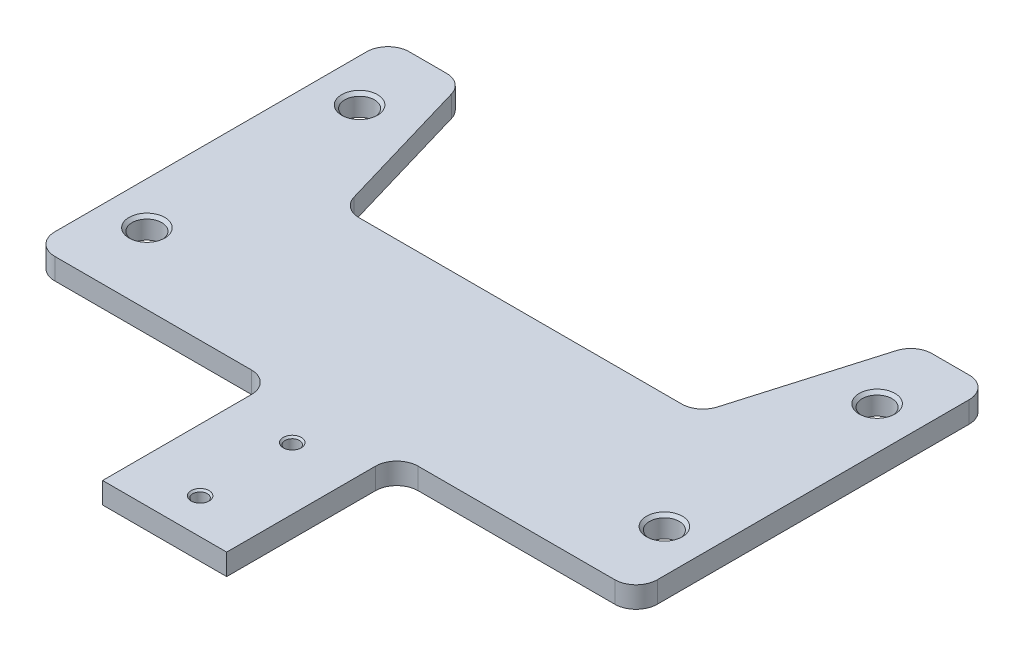
SolidWorks part; units mm, degrees
ref_plane "Front Plane" through (0, 0, 0) normal (0, 0, 1) x (1, 0, 0)
ref_plane "Top Plane" through (0, 0, 0) normal (0, 1, 0) x (1, 0, 0)
ref_plane "Right Plane" through (0, 0, 0) normal (1, 0, 0) x (0, 0, -1)
sketch "Sketch2" plane through (0, 0, 0) normal (0, 1, 0) x (1, 0, 0)
  line L1 (42.5, 0) -> (42.5, 50)
  line L2 (42.5, 50) -> (22.5, 50)
  line L3 (22.5, 50) -> (8.75, 26.1843)
  line L4 (8.75, 26.1843) -> (-8.75, 26.1843)
  line L5 (-8.75, 26.1843) -> (-22.5, 50)
  line L6 (-22.5, 50) -> (-42.5, 50)
  line L7 (-42.5, 50) -> (-42.5, 0)
  line L9 (-42.5, 0) -> (42.5, 0)
  point P0 (0, 26.1843)
  point P3 (0, 0)
  point P11 (32.5, 50)
  point P13 (-32.5, 50)
  dimension "D1" = 17.5
  dimension "D2" = 85
  dimension "D3" = 50
  dimension "D4" = 60
  dimension "D5" = 60
  dimension "D6" = 20
extrude "Boss-Extrude1" add sketch "Sketch2" along normal blind 3
sketch "Sketch3" plane through (0, 0, -26.1843) normal (0, 0, -1) x (-1, 0, 0)
  line L6 (-8.75, 0) -> (8.75, 0)
  line L7 (-8.75, 0) -> (-8.75, 1)
  line L8 (-8.75, 1) -> (8.75, 1)
  line L9 (8.75, 0) -> (8.75, 1)
  point P5 (0, 0)
  dimension "D1" = 17.5
  dimension "D2" = 1
extrude "Cut-Extrude1" [suppressed] cut sketch "Sketch3" against normal through all
sketch "Sketch10" plane through (0, 3, 0) normal (0, 1, 0) x (1, 0, 0)
  line L0 (-8.75, 0) -> (-8.75, -24)
  line L1 (-42.5, 0) -> (42.5, 0) construction
  line L2 (-8.75, -24) -> (8.75, -24)
  line L3 (8.75, -24) -> (8.75, 0)
  line L4 (8.75, 0) -> (-8.75, 0)
  point P4 (0, 0)
  dimension "D1" = 17.5
  dimension "D2" = 24
extrude "Boss-Extrude2" add sketch "Sketch10" against normal up to surface (3 mm away) up to face at (0, 0, -31.5461)
hole_wizard "M2.5x0.45 Tapped Hole1" positions "Sketch4" profile "Sketch5" tap size "M2.5x0.45" standard "ANSI Metric"
sketch "Sketch4" plane through (0, 3, 0) normal (0, 1, 0) x (1, 0, 0)
  line L4 (-8.75, -24) -> (8.75, -24) construction
  point P0 (0, -19)
  point P2 (0, -6)
  dimension "D1" = 13
  dimension "D2" = 5
  dimension "D3" = 8.75
sketch "Sketch5" plane through (0, 3, 19) normal (1, 0, 0) x (0, 0, 1)
  line L0 (0, 0) -> (0, 6.9659)
  line L1 (0, 6.9659) -> (1.025, 6.35)
  line L2 (1.025, 6.35) -> (1.025, 0.25)
  line L3 (1.025, 0.25) -> (1.275, 0)
  line L5 (1.275, 0) -> (0, 0)
  line L6 (-1.025, 0.25) -> (-1.275, 0) construction
  line L10 (0, 6.9659) -> (-1.025, 6.35) construction
  line L11 (0, -6.35) -> (0, 107.95) construction
  dimension "Tap Drill Dia." = 2.05
  dimension "Tap Drill Depth" = 6.35
  dimension "Near C'Sink Dia." = 2.55
  dimension "Near C'Sink Angle" = 90
  dimension "Drill Angle" = 118
cosmetic thread "Hole Thread1" parameters "D1"=5, "D2"=2.5
cosmetic thread "Hole Thread2" parameters "D1"=5, "D2"=2.5
hole_wizard "M5x0.8 Tapped Hole1" positions "Sketch6" profile "Sketch7" tap size "M5x0.8" standard "ANSI Metric"
sketch "Sketch6" plane through (0, 3, 0) normal (0, 1, 0) x (1, 0, 0)
  line L1 (-22.5, 50) -> (-42.5, 50) construction
  line L2 (42.5, 50) -> (22.5, 50) construction
  line L3 (42.5, 0) -> (42.5, 50) construction
  line L4 (-42.5, 50) -> (-42.5, 0) construction
  line L5 (-42.5, 0) -> (-8.75, 0) construction
  point P0 (-36.5, 40)
  point P2 (36.5, 40)
  point P18 (-36.5, 10)
  point P20 (36.5, 10)
  dimension "D1" = 6
  dimension "D2" = 10
  dimension "D3" = 10
  dimension "D4" = 6
  dimension "D5" = 10
  dimension "D6" = 10
sketch "Sketch7" plane through (-36.5, 3, -40) normal (1, 0, 0) x (0, 0, 1)
  line L0 (0, 0) -> (0, 13.6618)
  line L1 (0, 13.6618) -> (2.1, 12.4)
  line L2 (2.1, 12.4) -> (2.1, 0.425)
  line L3 (2.1, 0.425) -> (2.525, 0)
  line L5 (2.525, 0) -> (0, 0)
  line L6 (-2.1, 0.425) -> (-2.525, 0) construction
  line L10 (0, 13.6618) -> (-2.1, 12.4) construction
  line L11 (0, -6.35) -> (0, 107.95) construction
  dimension "Tap Drill Dia." = 4.2
  dimension "Tap Drill Depth" = 12.4
  dimension "Near C'Sink Dia." = 5.05
  dimension "Near C'Sink Angle" = 90
  dimension "Drill Angle" = 118
cosmetic thread "Hole Thread3" parameters "D1"=10, "D2"=5
cosmetic thread "Hole Thread4" parameters "D1"=10, "D2"=5
cosmetic thread "Hole Thread5" parameters "D1"=10, "D2"=5
cosmetic thread "Hole Thread6" parameters "D1"=10, "D2"=5
sketch "Sketch8" plane through (0, 0, -26.1843) normal (0, 0, -1) x (-1, 0, 0)
  line L5 (-8.75, 3) -> (-8.75, 0) construction
  line L6 (-13, 0) -> (-8.75, 0)
  line L7 (-13, 0) -> (-13, 1.3)
  line L8 (-13, 1.3) -> (-8.75, 1.3)
  line L9 (-8.75, 0) -> (-8.75, 1.3)
  line L10 (0, 0) -> (0, 12.6228) construction
  line L11 (8.75, 0) -> (8.75, 1.3)
  line L12 (13, 1.3) -> (8.75, 1.3)
  line L13 (13, 0) -> (13, 1.3)
  line L14 (13, 0) -> (8.75, 0)
  line L15 (-22.5, 0) -> (-8.75, 0) construction
  dimension "D1" = 4.25
  dimension "D2" = 1.3
extrude "Cut-Extrude2" [suppressed] cut sketch "Sketch8" against normal through all both and the other way through all
sketch "Sketch9" plane through (0, 0, 0) normal (0, -1, 0) x (1, 0, 0)
  line L0 (-32, -50) -> (-25, -26.1843)
  line L1 (-22.5, -50) -> (-42.5, -50) construction
  line L3 (25, -26.1843) -> (32, -50)
  line L4 (42.5, -50) -> (22.5, -50) construction
  line L5 (32, -50) -> (-32, -50)
  line L6 (-25, -26.1843) -> (25, -26.1843)
  line L7 (8.75, -26.1843) -> (-8.75, -26.1843) construction
  point P8 (0, -50)
  point P12 (0, -26.1843)
  dimension "D1" = 64
  dimension "D2" = 50
extrude "Cut-Extrude3" cut sketch "Sketch9" against normal through all
fillet "Fillet1" radius 3 10 edges at (42.5, 1.5, -50) (-42.5, 1.5, -50) (-32, 1.5, -50) (32, 1.5, -50) (25, 1.5, -26.1843) (-25, 1.5, -26.1843) (42.5, 1.5, 0) (-42.5, 1.5, 0) (8.75, 1.5, 0) (-8.75, 1.5, 0)
fillet "Fillet2" [suppressed] radius 1
